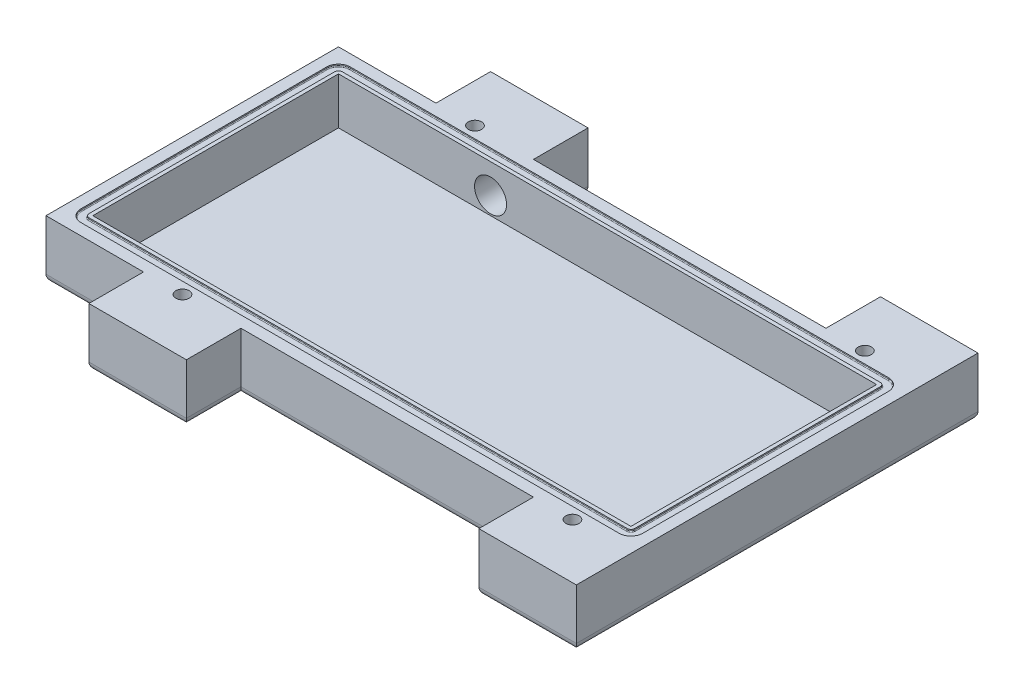
SolidWorks part; units mm, degrees
ref_plane "Front Plane" through (0, 0, 0) normal (0, 0, 1) x (1, 0, 0)
ref_plane "Top Plane" through (0, 0, 0) normal (0, 1, 0) x (1, 0, 0)
ref_plane "Right Plane" through (0, 0, 0) normal (1, 0, 0) x (0, 0, -1)
sketch "Sketch1" plane through (0, 0, 0) normal (0, 1, 0) x (1, 0, 0)
  line L1 (0, 0) -> (150, 0)
  line L2 (0, 0) -> (0, 75)
  line L3 (0, 75) -> (150, 75)
  line L4 (150, 0) -> (150, 75)
  dimension "D1" = 150
  dimension "D2" = 75
extrude "Boss-Extrude1" add sketch "Sketch1" along normal blind 15
sketch "Sketch5" plane through (0, 15, 0) normal (0, 1, 0) x (1, 0, 0)
  line L11 (6, 69) -> (6, 6)
  line L12 (6, 6) -> (144, 6)
  line L13 (144, 6) -> (144, 69)
  line L14 (144, 69) -> (6, 69)
  line L15 (6, 69) -> (6, 6)
  line L16 (6, 6) -> (144, 6)
  line L17 (144, 6) -> (144, 69)
  line L18 (144, 69) -> (6, 69)
  dimension "D1" = 6
extrude "Cut-Extrude2" cut sketch "Sketch5" against normal blind 12
ref_plane "Plane1" through (0, 0, -37.5) normal (0, 0, -1) x (-1, 0, 0)
sketch "Sketch2" plane through (0, 0, 0) normal (0, 0, 1) x (1, 0, 0)
  line L0 (0, 15) -> (150, 15) construction
  line L1 (150, 0) -> (125, 0)
  line L2 (150, 0) -> (150, 15)
  line L3 (150, 15) -> (125, 15)
  line L4 (125, 0) -> (125, 15)
  line L5 (0, 0) -> (150, 0) construction
  line L6 (50, 0) -> (25, 0)
  line L7 (50, 0) -> (50, 15)
  line L8 (50, 15) -> (25, 15)
  line L9 (25, 0) -> (25, 15)
  line L10 (0, 15) -> (0, 0) construction
  dimension "D1" = 25
  dimension "D2" = 25
  dimension "D3" = 25
extrude "Boss-Extrude2" add sketch "Sketch2" along normal blind 14
sketch "Sketch3" plane through (25, 0, 0) normal (-1, 0, 0) x (0, 0, 1)
  line L0 (0, 0) -> (14, 15) construction
  circle A0 centre (7, 7.5) radius 4.1
  point P4 (7, 7.5)
  dimension "D1" = 8.2
sketch "Sketch6" plane through (0, 3, 0) normal (0, 1, 0) x (1, 0, 0)
  line L0 (25, -14) -> (25, 0) construction
  line L1 (50, -14) -> (50, 0) construction
  line L2 (50, -14) -> (25, -14) construction
  line L3 (25, -14) -> (25, 0) construction
  line L4 (50, -14) -> (50, 0) construction
  line L5 (50, -14) -> (25, -14) construction
  line L6 (25, -7) -> (45, -7) construction
  line L7 (45, -7) -> (45, 6) construction
  line L8 (25, -7) -> (40, -7)
  line L9 (45, -2) -> (45, 6)
  arc A0 (40, -7) -> (45, -2) centre (40, -2) ccw
  point P6 (40, -7)
  dimension "D1" = 5
  dimension "D2" = 5
  dimension "D3" = 8
sweep "Cut-Sweep1" cut profiles "Sketch3" path "Sketch6"
sketch "Sketch7" plane through (125, 0, 0) normal (-1, 0, 0) x (0, 0, 1)
  line L0 (0, 0) -> (14, 15) construction
  circle A0 centre (7, 7.5) radius 4.1
  point P4 (7, 7.5)
  dimension "D1" = 8.2
sketch "Sketch8" plane through (0, 3, 0) normal (0, 1, 0) x (1, 0, 0)
  line L0 (150, -14) -> (150, 75) construction
  line L1 (150, -14) -> (125, -14) construction
  line L2 (125, -14) -> (125, 0) construction
  line L3 (150, -14) -> (150, 75) construction
  line L4 (150, -14) -> (125, -14) construction
  line L5 (125, -14) -> (125, 0) construction
  line L6 (125, -7) -> (145, -7) construction
  line L7 (145, -7) -> (145, 6) construction
  line L8 (125, -7) -> (140, -7)
  line L9 (145, -2) -> (145, 6)
  arc A0 (140, -7) -> (145, -2) centre (140, -2) ccw
  point P6 (140, -7)
  point P8 (145, -2)
  dimension "D1" = 5
  dimension "D2" = 5
  dimension "D3" = 5
  dimension "D4" = 13
sweep "Cut-Sweep2" cut profiles "Sketch7" path "Sketch8"
chamfer "Chamfer3" distance 2 angle 80 1 edges at (144, 7.5, -6) first distance on face at (146.55, 7.5, -6)
mirror "Mirror1" about plane through (0, 0, -37.5) normal (0, 0, -1) of "Boss-Extrude2", "Cut-Sweep1", "Cut-Sweep2"
sketch "Sketch10" plane through (0, 15, 0) normal (0, 1, 0) x (1, 0, 0)
  line L30 (4, 4) -> (146, 4)
  line L31 (4, 71) -> (4, 4)
  line L32 (146, 71) -> (4, 71)
  line L33 (146, 4) -> (146, 71)
  line L34 (6, 4) -> (144, 4)
  line L35 (4, 69) -> (4, 6)
  line L36 (144, 71) -> (6, 71)
  line L37 (146, 6) -> (146, 69)
  arc A0 (144, 4) -> (146, 6) centre (144, 6) ccw
  arc A1 (144, 71) -> (146, 69) centre (144, 69) cw
  arc A2 (4, 69) -> (6, 71) centre (6, 69) cw
  arc A3 (6, 4) -> (4, 6) centre (6, 6) cw
  dimension "D2" = 2
  dimension "D1" = 2
sketch "Sketch11" plane through (0, 0, -37.5) normal (0, 0, -1) x (-1, 0, 0)
  line L1 (-144, 15) -> (-146, 15) construction
  line L2 (-144, 15) -> (-146, 15) construction
  line L4 (-146.85, 14.5) -> (-145.15, 14.5)
  line L5 (-147.05, 14.7) -> (-147.05, 15.5)
  line L6 (-147.05, 15.5) -> (-144.95, 15.5)
  line L7 (-144.95, 14.7) -> (-144.95, 15.5)
  line L8 (-147.05, 14.5) -> (-144.95, 15.5) construction
  line L9 (-147.05, 15.5) -> (-144.95, 14.5) construction
  arc A0 (-145.15, 14.5) -> (-144.95, 14.7) centre (-145.15, 14.7) ccw
  arc A1 (-146.85, 14.5) -> (-147.05, 14.7) centre (-146.85, 14.7) cw
  dimension "D1" = 1
  dimension "D3" = 0.2
  dimension "D2" = 2.1
sweep "Cut-Sweep3" cut profiles "Sketch11" path "Sketch10"
fillet "Fillet3" radius 2 16 edges at (25, 0, -82) (37.5, 0, -89) (50, 0, -82) (137.5, 0, -89) (150, 0, -37.5) (137.5, 0, 14) (50, 0, 7) (37.5, 0, 14) (25, 0, 7) (0, 0, -37.5)
chamfer "Chamfer4" distance 2 angle 80 1 edges at (144, 7.5, -69) first distance on face at (146.55, 7.5, -69)
ref_plane "Plane2" through (6, 3, -6) normal (0, 0, 1) x (1, 0, 0)
sketch "Sketch13" plane through (0, 15, 0) normal (0, 1, 0) x (1, 0, 0)
  line L0 (25, 0) -> (50, 0)
  line L1 (125, 0) -> (150, 0) construction
  line L2 (150, -14) -> (150, 89) construction
  line L3 (125, 75) -> (150, 75) construction
  line L4 (25, 75) -> (50, 75) construction
  point P17 (35, 75)
  point P18 (135, 75)
  point P19 (35, 0)
  point P20 (135, 0)
  dimension "D1" = 10
  dimension "D2" = 10
hole_wizard "CBORE for M3 Hex Head Cap Screw1" positions "Sketch18" profile "Sketch16" counterbore size "M3" standard "ISO" end condition through all
sketch "Sketch18" plane through (0, 0, 0) normal (0, -1, 0) x (-1, 0, 0)
  point P0 (-35, 0)
  point P3 (-35, 75)
  point P6 (-135, 75)
  point P9 (-135, 0)
sketch "Sketch16" plane through (35, 0, 0) normal (1, 0, 0) x (0, 0, -1)
  line L0 (0, 0) -> (0, 15.0001)
  line L1 (0, 15.0001) -> (1.7, 15.0001)
  line L3 (1.7, 15.0001) -> (1.7, 2)
  line L4 (1.7, 2) -> (4.6755, 2)
  line L5 (4.6755, 2) -> (4.6755, 0)
  line L7 (4.6755, 0) -> (0, 0)
  line L11 (0, -6.35) -> (0, 107.95) construction
  dimension "Thru Hole Dia." = 3.4
  dimension "Thru Hole Depth" = 15.0001
  dimension "C'Bore Dia." = 9.351
  dimension "C'Bore Depth" = 2
